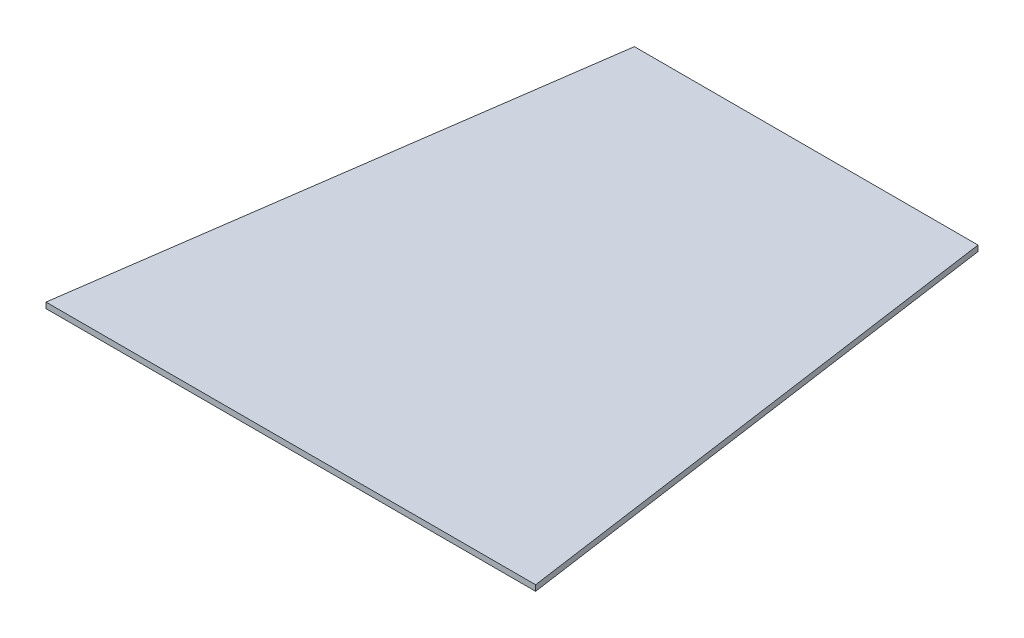
SolidWorks part; units mm, degrees
ref_plane "前视基准面" through (0, 0, 0) normal (0, 0, 1) x (1, 0, 0)
ref_plane "上视基准面" through (0, 0, 0) normal (0, 1, 0) x (1, 0, 0)
ref_plane "右视基准面" through (0, 0, 0) normal (1, 0, 0) x (0, 0, -1)
other "Configuration Table"
sketch "草图1" plane through (0, 0, 0) normal (0, 1, 0) x (1, 0, 0)
  line L0 (0, 0) -> (0, 90) construction
  line L1 (30, 90) -> (-30, 90)
  line L2 (-30, 90) -> (-42.75, 0)
  line L3 (-42.75, 0) -> (42.75, 0)
  line L4 (30, 90) -> (42.75, 0)
  dimension "D1" = 42.75
  dimension "D2" = 90
  dimension "D3" = 30
extrude "凸台-拉伸1" add sketch "草图1" along normal blind 1
